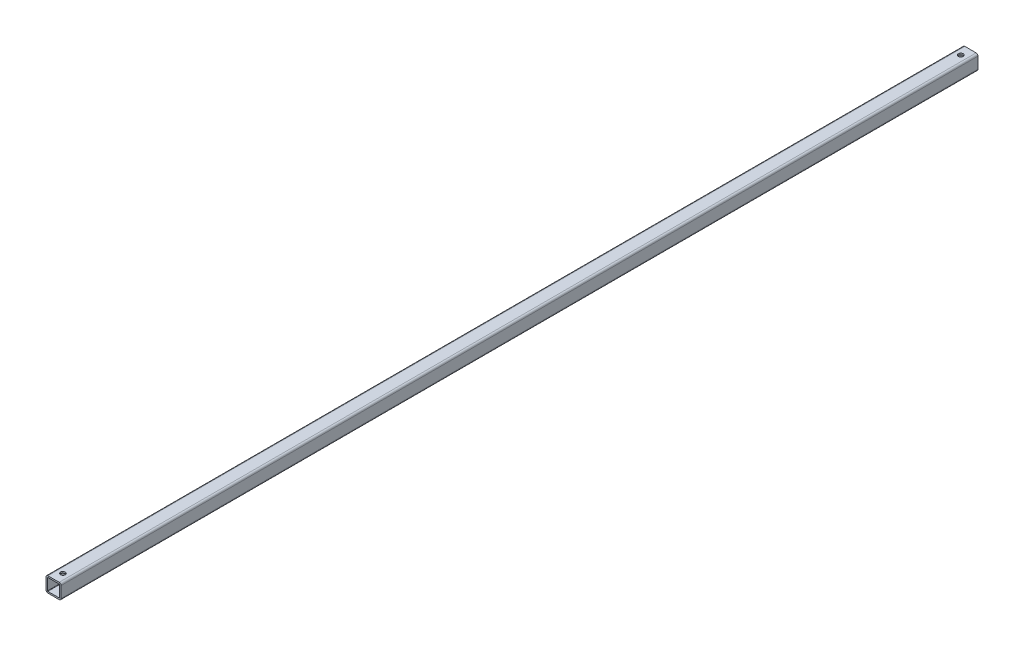
SolidWorks part; units mm, degrees
material "6063-T4"
ref_plane "Front Plane" through (0, 0, 0) normal (0, 0, 1) x (1, 0, 0)
ref_plane "Top Plane" through (0, 0, 0) normal (0, 1, 0) x (1, 0, 0)
ref_plane "Right Plane" through (0, 0, 0) normal (1, 0, 0) x (0, 0, -1)
sketch "Sketch1" plane through (0, 0, 0) normal (0, 0, 1) x (1, 0, 0)
  line L1 (7.5, -10) -> (-7.5, -10)
  line L2 (10, -7.5) -> (10, 7.5)
  line L3 (7.5, 10) -> (-7.5, 10)
  line L4 (-10, -7.5) -> (-10, 7.5)
  line L5 (10, -10) -> (-10, 10) construction
  line L6 (10, 10) -> (-10, -10) construction
  arc A0 (-7.5, 10) -> (-10, 7.5) centre (-7.5, 7.5) ccw
  arc A1 (10, 7.5) -> (7.5, 10) centre (7.5, 7.5) ccw
  arc A2 (7.5, -10) -> (10, -7.5) centre (7.5, -7.5) ccw
  arc A3 (-7.5, -10) -> (-10, -7.5) centre (-7.5, -7.5) cw
  point P0 (0, 0)
  dimension "D2" = 2.5
  dimension "D1" = 20
extrude "Extrude-Thin1" add sketch "Sketch1" along normal mid plane 1219.2 thin thin type one direction reverse wall 2
hole_wizard "1/4 (0.25) Diameter Hole1" positions "Sketch4" profile "Sketch5" hole size "1/4" standard "ANSI Inch"
sketch "Sketch4" plane through (0, 10, 0) normal (0, 1, 0) x (1, 0, 0)
  point P0 (-0.2, 596.9)
  point P3 (-0.2, -596.9)
sketch "Sketch5" plane through (-0.2, 10, -596.9) normal (1, 0, 0) x (0, 0, 1)
  line L0 (0, 0) -> (0, 27.3077)
  line L1 (0, 27.3077) -> (3.175, 25.4)
  line L2 (3.175, 25.4) -> (3.175, 0)
  line L5 (3.175, 0) -> (0, 0)
  line L10 (0, 27.3077) -> (-3.175, 25.4) construction
  line L11 (0, -6.35) -> (0, 107.95) construction
  dimension "Hole Dia." = 6.35
  dimension "Hole Depth" = 25.4
  dimension "Drill Angle" = 118
equation "\"D2@Sketch1\" = \"D5@Extrude-Thin1\" * 1.25"
